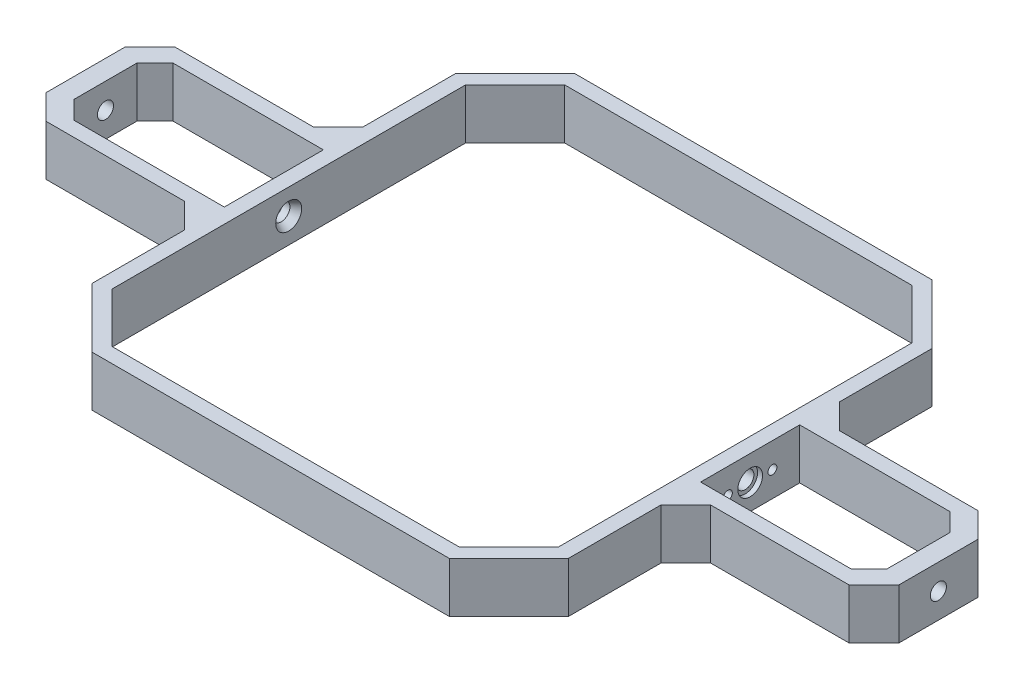
SolidWorks part; units mm, degrees
ref_plane "Front Plane" through (0, 0, 0) normal (0, 0, 1) x (1, 0, 0)
ref_plane "Top Plane" through (0, 0, 0) normal (0, 1, 0) x (1, 0, 0)
ref_plane "Right Plane" through (0, 0, 0) normal (1, 0, 0) x (0, 0, -1)
sketch "Sketch2" plane through (0, 0, 0) normal (0, 1, 0) x (1, 0, 0)
  line L0 (-48.085, 48.72) -> (48.085, 48.72)
  line L1 (-45.085, -45.72) -> (45.085, -45.72)
  line L2 (-45.085, -45.72) -> (-45.085, 45.72)
  line L3 (-45.085, 45.72) -> (45.085, 45.72)
  line L4 (45.085, -45.72) -> (45.085, 45.72)
  line L5 (-45.085, -45.72) -> (45.085, 45.72) construction
  line L6 (-45.085, 45.72) -> (45.085, -45.72) construction
  line L7 (48.085, -48.72) -> (48.085, 48.72)
  line L8 (-48.085, -48.72) -> (48.085, -48.72)
  line L9 (-48.085, -48.72) -> (-48.085, 48.72)
  point P0 (0, 0)
  dimension "D1" = 90.17
  dimension "D2" = 91.44
  dimension "D3" = 3
extrude "Boss-Extrude1" add sketch "Sketch2" along normal blind 5.08 and the other way blind 5.08
sketch "Sketch3" plane through (48.085, 0, 0) normal (1, 0, 0) x (0, 0, -1)
  line L0 (0, -5.08) -> (0, 5.08) construction
  line L1 (-48.72, 5.08) -> (48.72, 5.08) construction
  line L2 (-48.72, -5.08) -> (48.72, -5.08) construction
  circle A0 centre (0, 0) radius 1.75
  dimension "D1" = 3.5
extrude "Cut-Extrude1" cut sketch "Sketch3" against normal through all
sketch "Sketch4" plane through (45.085, 0, 0) normal (-1, 0, 0) x (0, 0, 1)
  line L0 (0, 0) -> (-4.5, 0) construction
  line L1 (0, 0) -> (0, 3.3068) construction
  circle A0 centre (-4.5, 0) radius 1.75
  circle A1 centre (4.5, 0) radius 1.75
  dimension "D1" = 9
  dimension "D2" = 3.5
extrude "Cut-Extrude2" cut sketch "Sketch4" against normal blind 1
sketch "Sketch5" plane through (46.085, 0, 0) normal (-1, 0, 0) x (0, 0, 1)
  line L0 (0, 0) -> (0, 7.4728) construction
  circle A0 centre (-4.5, 0) radius 0.9
  circle A1 centre (4.5, 0) radius 0.9
  dimension "D1" = 1.8
extrude "Cut-Extrude3" cut sketch "Sketch5" against normal through all
sketch "Sketch6" plane through (48.085, 0, 0) normal (1, 0, 0) x (0, 0, -1)
  circle A0 centre (0, 0) radius 2.5
  dimension "D1" = 5
extrude "Cut-Extrude4" cut sketch "Sketch6" against normal blind 1
sketch "Sketch8" plane through (0, 5.08, 0) normal (0, 1, 0) x (1, 0, 0)
  line L0 (48.085, 0) -> (63.085, 0) construction
  line L1 (48.085, -48.72) -> (48.085, 48.72) construction
  line L2 (81.085, 13) -> (45.085, 13)
  line L3 (78.085, -10) -> (48.085, -10)
  line L4 (78.085, -10) -> (78.085, 10)
  line L5 (78.085, 10) -> (48.085, 10)
  line L6 (48.085, -10) -> (48.085, 10)
  line L7 (78.085, -10) -> (48.085, 10) construction
  line L8 (78.085, 10) -> (48.085, -10) construction
  line L9 (45.085, -13) -> (45.085, 13)
  line L10 (81.085, -13) -> (45.085, -13)
  line L11 (81.085, -13) -> (81.085, 13)
  line L12 (48.085, 10) -> (48.085, 13)
  line L13 (48.085, -10) -> (48.085, -13)
  line L14 (0, 0) -> (0, 20.6894) construction
  line L15 (-78.085, 10) -> (-48.085, -10) construction
  line L16 (-78.085, -10) -> (-48.085, 10) construction
  line L17 (-48.085, 0) -> (-63.085, 0) construction
  line L18 (-86.085, 13) -> (-86.085, -13)
  line L19 (-81.085, -13) -> (-86.085, -13)
  line L20 (-81.085, 13) -> (-81.085, -13)
  line L21 (-81.085, 13) -> (-86.085, 13)
  line L22 (-48.085, -10) -> (-48.085, -13)
  line L23 (-48.085, 10) -> (-48.085, 13)
  line L24 (-81.085, -13) -> (-81.085, 13)
  line L25 (-81.085, -13) -> (-45.085, -13)
  line L26 (-45.085, -13) -> (-45.085, 13)
  line L27 (-48.085, -10) -> (-48.085, 10)
  line L28 (-78.085, 10) -> (-48.085, 10)
  line L29 (81.085, 13) -> (86.085, 13)
  line L30 (81.085, 13) -> (81.085, -13)
  line L31 (81.085, -13) -> (86.085, -13)
  line L32 (86.085, 13) -> (86.085, -13)
  line L33 (-78.085, -10) -> (-78.085, 10)
  line L34 (-78.085, -10) -> (-48.085, -10)
  line L35 (-81.085, 13) -> (-45.085, 13)
  line M1 (-48.085, 48.72) -> (-48.085, -48.72)
  line M3 (48.085, -48.72) -> (48.085, 48.72)
  dimension "D2" = 30
  dimension "D3" = 20
  dimension "D4" = 5
  dimension "D1" = 3
extrude "Boss-Extrude2" add sketch "Sketch8" against normal up to surface (10.16 mm away) contours L35 L34 M1 | L10 L11 L2 L5 L4 L3 M3 | L20 L21 L18 L19 | L32 L29 L11 L31 region at (80.6649, 5.08, 0) region at (83.585, 5.08, 0) region at (-83.585, 5.08, 0) region at (-64.585, 5.08, -12.5799) up to face at (0, -5.08, 0)
chamfer "Chamfer1" distance 1.5 angle 30 1 edges at (-45.085, 0, 1.75) first distance on face at (-48.085, 0, -1.75)
sketch "Sketch9" plane through (-86.085, 0, 0) normal (-1, 0, 0) x (0, 0, 1)
  line L0 (0, 5.08) -> (0, -5.08) construction
  line L1 (-13, 5.08) -> (13, 5.08) construction
  line L2 (-13, -5.08) -> (13, -5.08) construction
  circle A0 centre (0, 0) radius 1.625
  dimension "D1" = 3.25
extrude "Cut-Extrude5" cut sketch "Sketch9" against normal blind 5
mirror "Mirror2" about plane through (0, 0, 0) normal (1, 0, 0) of "Cut-Extrude5"
chamfer "Chamfer3" distance 10 angle 45 4 edges at (45.085, 0, 45.72) (45.085, 0, -45.72) (-45.085, 0, -45.72) (-45.085, 0, 45.72)
chamfer "Chamfer4" distance 12 angle 45 4 edges at (-48.085, 0, -48.72) (48.085, 0, -48.72) (-48.085, 0, 48.72) (48.085, 0, 48.72)
chamfer "Chamfer5" distance 5 angle 45 8 edges at (-48.085, 0, 13) (-86.085, 0, 13) (-86.085, 0, -13) (-48.085, 0, -13) (48.085, 0, -13) (48.085, 0, 13) (86.085, 0, -13) (86.085, 0, 13)
sketch "Sketch10" plane through (0, 5.08, 0) normal (0, 1, 0) x (1, 0, 0)
  line L1 (78.085, -10) -> (98.085, -10)
  line L2 (78.085, -10) -> (78.085, 10)
  line L3 (78.085, 10) -> (98.085, 10)
  line L4 (98.085, -10) -> (98.085, 10)
  line L11 (0, 0) -> (0, 29.6145) construction
  line L12 (-78.2566, -10.1716) -> (-82.085, -6.3431)
  line L13 (-82.085, 6.3431) -> (-78.2566, 10.1716)
  line L14 (82.085, -6.3431) -> (82.085, 6.3431)
  line L15 (82.085, 6.3431) -> (78.2566, 10.1716)
  line L16 (78.2566, -10.1716) -> (82.085, -6.3431)
  line L17 (82.085, -6.3431) -> (82.085, 6.3431)
  line L18 (82.085, 6.3431) -> (78.2566, 10.1716)
  line L19 (78.2566, -10.1716) -> (82.085, -6.3431)
  line L20 (-82.085, -6.3431) -> (-82.085, 6.3431)
  line L21 (-98.085, -10) -> (-98.085, 10)
  line L22 (-78.085, 10) -> (-98.085, 10)
  line L23 (-78.085, -10) -> (-78.085, 10)
  line L24 (-78.085, -10) -> (-98.085, -10)
  line M7 (78.085, 10) -> (78.085, -10)
  line M34 (-78.085, -10) -> (-78.085, 10)
  dimension "D2" = 20
  dimension "D1" = 4
extrude "Cut-Extrude6" cut sketch "Sketch10" against normal through all contours L1 L19 L17 L18 L3 M7 | L24 L22 L13 L20 L12 M34 region at (79.9282, 5.08, 0) region at (-79.9282, 5.08, 0)
